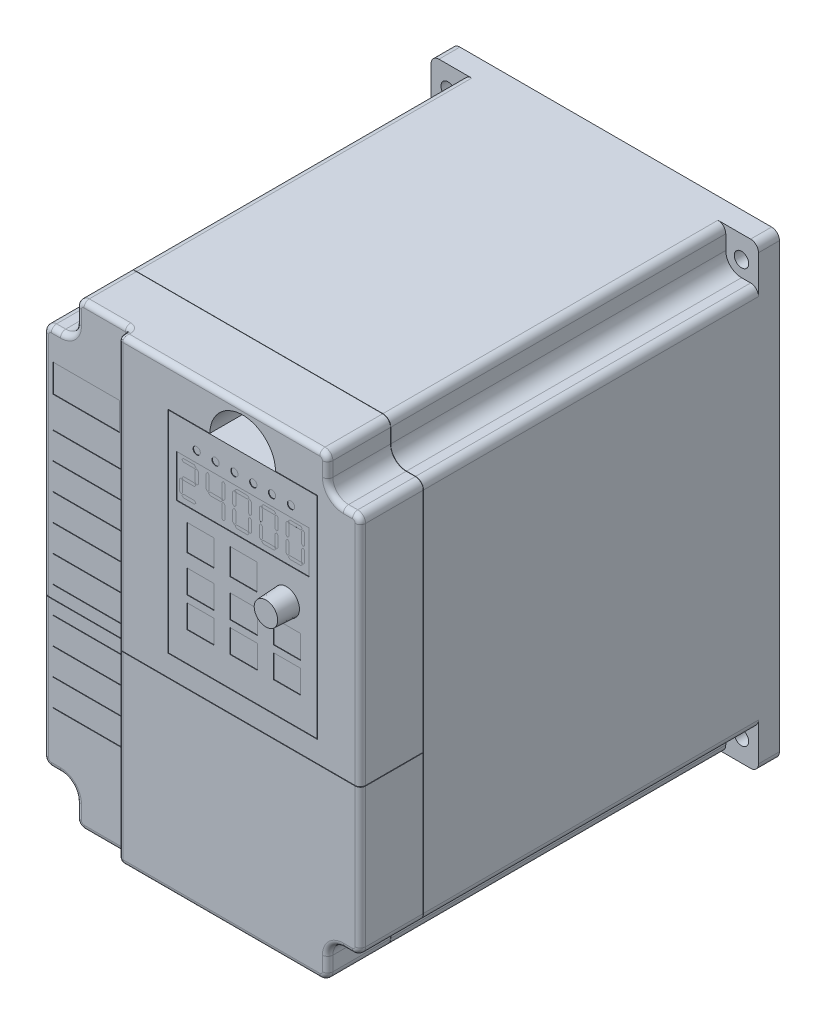
SolidWorks part; units mm, degrees
ref_plane "Front Plane" through (0, 0, 0) normal (0, 0, 1) x (1, 0, 0)
ref_plane "Top Plane" through (0, 0, 0) normal (0, 1, 0) x (1, 0, 0)
ref_plane "Right Plane" through (0, 0, 0) normal (1, 0, 0) x (0, 0, -1)
sketch "Sketch1" plane through (0, 0, 0) normal (0, 0, 1) x (1, 0, 0)
  line L1 (-62.5, -87.5) -> (62.5, -87.5)
  line L2 (-62.5, -87.5) -> (-62.5, 87.5)
  line L3 (-62.5, 87.5) -> (62.5, 87.5)
  line L4 (62.5, -87.5) -> (62.5, 87.5)
  line L5 (0, 87.5) -> (0, -87.5) construction
  line L6 (-62.5, 0) -> (62.5, 0) construction
  point P0 (0, 0)
  dimension "D1" = 125
  dimension "D2" = 175
extrude "Boss-Extrude1" add sketch "Sketch1" along normal blind 160
sketch "Sketch2" plane through (0, 0, 160) normal (0, 0, 1) x (1, 0, 0)
  line L1 (56, -79) -> (-56, -79) construction
  line L2 (56, -79) -> (56, 79) construction
  line L3 (56, 79) -> (-56, 79) construction
  line L4 (-56, -79) -> (-56, 79) construction
  line L5 (0, 79) -> (0, -79) construction
  line L6 (56, 0) -> (-56, 0) construction
  circle A0 centre (-56, 79) radius 2.75
  circle A1 centre (56, 79) radius 2.75
  circle A2 centre (-56, -79) radius 2.75
  circle A3 centre (56, -79) radius 2.75
  point P0 (0, 0)
  dimension "D1" = 5.5
  dimension "D2" = 112
  dimension "D3" = 158
extrude "Cut-Extrude1" cut sketch "Sketch2" against normal through all
sketch "Sketch3" plane through (0, 0, 160) normal (0, 0, 1) x (1, 0, 0)
  line L0 (-50, 79) -> (-50, 87.5)
  line L1 (62.5, 87.5) -> (-62.5, 87.5) construction
  line L2 (-50, 87.5) -> (-62.5, 87.5)
  line L3 (-62.5, 87.5) -> (-62.5, 73)
  line L4 (-62.5, 87.5) -> (-62.5, -87.5) construction
  line L5 (-62.5, 73) -> (-56, 73)
  line L6 (0, 87.5) -> (0, -87.5) construction
  line L7 (-62.5, -87.5) -> (62.5, -87.5) construction
  line L8 (-62.5, 0) -> (62.5, 0) construction
  line L9 (62.5, -87.5) -> (62.5, 87.5) construction
  line L10 (62.5, 73) -> (56, 73)
  line L11 (62.5, 87.5) -> (62.5, 73)
  line L12 (50, 87.5) -> (62.5, 87.5)
  line L13 (50, 79) -> (50, 87.5)
  line L14 (50, -79) -> (50, -87.5)
  line L15 (50, -87.5) -> (62.5, -87.5)
  line L16 (62.5, -87.5) -> (62.5, -73)
  line L17 (62.5, -73) -> (56, -73)
  line L18 (-62.5, -73) -> (-56, -73)
  line L19 (-62.5, -87.5) -> (-62.5, -73)
  line L20 (-50, -87.5) -> (-62.5, -87.5)
  line L21 (-50, -79) -> (-50, -87.5)
  arc A0 (-56, 73) -> (-50, 79) centre (-56, 79) ccw
  arc A1 (56, 73) -> (50, 79) centre (56, 79) cw
  arc A2 (56, -73) -> (50, -79) centre (56, -79) ccw
  arc A3 (-56, -73) -> (-50, -79) centre (-56, -79) cw
  dimension "D1" = 6
extrude "Cut-Extrude2" cut sketch "Sketch3" against normal offset from surface (152 mm away) 8 up to face at (58.75, 79, 0)
sketch "Sketch4" plane through (0, 0, 160) normal (0, 0, 1) x (1, 0, 0)
  line L0 (-21.4754, 179.91) -> (260.5246, 179.91) construction
  line L2 (-29.6938, 97.8376) -> (-77.9459, 97.8376)
  line L3 (-29.6938, 97.8376) -> (-29.6938, -104.6749)
  line L4 (-29.6938, -104.6749) -> (-77.9459, -104.6749)
  line L5 (-77.9459, 97.8376) -> (-77.9459, -104.6749)
  line L6 (-53.8199, -104.6749) -> (-53.8199, 97.8376) construction
  line L7 (-29.6938, -3.4186) -> (-77.9459, -3.4186) construction
  point P206 (-53.8199, -3.4186)
extrude "Cut-Extrude3" cut sketch "Sketch4" against normal blind 4
fillet "Fillet3" radius 1.5 2 edges at (-29.6938, 0, 160) (-29.6938, 0, 156)
fillet "Fillet1" radius 3 12 edges at (-50, 87.5, 82) (-62.5, 73, 82) (-62.5, -73, 82) (-50, -87.5, 82) (50, -87.5, 84) (62.5, -73, 84) (62.5, 73, 84) (50, 87.5, 84) (-62.5, -87.5, 4) (62.5, -87.5, 4) (62.5, 87.5, 4) (-62.5, 87.5, 4)
fillet "Fillet2" radius 2 32 edges at (49.1213, 86.6213, 160) (50, 81.75, 160) (51.7574, 74.7574, 160) (57.75, 73, 160) (61.6213, 72.1213, 160) (62.5, 0, 160) (61.6213, -72.1213, 160) (57.75, -73, 160) (51.7574, -74.7574, 160) (50, -81.75, 160) (49.1213, -86.6213, 160) (9.4031, -87.5, 160) (9.4031, 87.5, 160) (-29.2545, -87.5, 159.5607) (-30.1332, -87.5, 156.4393) (-29.2545, 87.5, 159.5607) (-30.1332, 87.5, 156.4393) (-39.0969, -87.5, 156) (-49.1213, -86.6213, 156) (-50, -81.75, 156) (-51.7574, -74.7574, 156) (-57.75, -73, 156) (-61.6213, -72.1213, 156) (-62.5, 0, 156) (-61.6213, 72.1213, 156) (-57.75, 73, 156) (-51.7574, 74.7574, 156) (-50, 81.75, 156) (-49.1213, 86.6213, 156) (-39.0969, 87.5, 156) (-29.6938, -87.5, 158) (-29.6938, 87.5, 158)
sketch "Sketch5" plane through (0, 0, 160) normal (0, 0, 1) x (1, 0, 0)
  line L0 (78.7819, -16.7409) -> (-90.6907, -16.7409)
  line L1 (12.798, 23.1824) -> (12.798, 14.2684)
  line L2 (-10.721, 71.8528) -> (45.8698, 71.8528)
  line L3 (-10.721, 71.8528) -> (-10.721, -8.4272)
  line L4 (-10.721, -8.4272) -> (45.8698, -8.4272)
  line L5 (45.8698, 71.8528) -> (45.8698, -8.4272)
  line L6 (17.5744, -8.4272) -> (17.5744, 71.8528) construction
  line L7 (-10.721, 31.7128) -> (45.8698, 31.7128) construction
  line L8 (-7.7964, 59.7158) -> (42.9452, 59.7158)
  line L9 (-7.7964, 59.7158) -> (-7.7964, 43.4843)
  line L10 (-7.7964, 43.4843) -> (42.9452, 43.4843)
  line L11 (42.9452, 59.7158) -> (42.9452, 43.4843)
  line L12 (17.5744, 43.4843) -> (17.5744, 59.7158) construction
  line L13 (-7.7964, 51.6) -> (42.9452, 51.6) construction
  line L14 (-3.702, 38.2497) -> (6.6803, 38.2497)
  line L15 (-3.702, 38.2497) -> (-3.702, 28.2467)
  line L16 (-3.702, 28.2467) -> (6.6803, 28.2467)
  line L17 (6.6803, 38.2497) -> (6.6803, 28.2467)
  line L18 (1.4891, 28.2467) -> (1.4891, 38.2497) construction
  line L19 (-3.702, 33.2482) -> (6.6803, 33.2482) construction
  line L20 (12.6404, 38.5061) -> (23.0227, 38.5061)
  line L21 (12.6404, 38.5061) -> (12.6404, 28.5031)
  line L22 (12.6404, 28.5031) -> (23.0227, 28.5031)
  line L23 (23.0227, 38.5061) -> (23.0227, 28.5031)
  line L24 (17.8316, 28.5031) -> (17.8316, 38.5061) construction
  line L25 (12.6404, 33.5046) -> (23.0227, 33.5046) construction
  line L26 (-3.702, 23.1824) -> (6.6803, 23.1824)
  line L27 (-3.702, 23.1824) -> (-3.702, 14.2684)
  line L28 (-3.702, 14.2684) -> (6.6803, 14.2684)
  line L29 (6.6803, 23.1824) -> (6.6803, 14.2684)
  line L30 (1.4891, 14.2684) -> (1.4891, 23.1824) construction
  line L31 (-3.702, 18.7254) -> (6.6803, 18.7254) construction
  line L32 (12.798, 23.1824) -> (23.1803, 23.1824)
  line L33 (23.1803, 23.1824) -> (23.1803, 14.2684)
  line L34 (12.798, 14.2684) -> (23.1803, 14.2684)
  line L35 (29.298, 23.1824) -> (29.298, 14.2684)
  line L36 (29.298, 23.1824) -> (39.6803, 23.1824)
  line L37 (39.6803, 23.1824) -> (39.6803, 14.2684)
  line L38 (29.298, 14.2684) -> (39.6803, 14.2684)
  line L39 (12.798, 11.6824) -> (12.798, 2.7684)
  line L40 (12.798, 11.6824) -> (23.1803, 11.6824)
  line L41 (23.1803, 11.6824) -> (23.1803, 2.7684)
  line L42 (12.798, 2.7684) -> (23.1803, 2.7684)
  line L43 (29.298, 11.6824) -> (29.298, 2.7684)
  line L44 (29.298, 11.6824) -> (39.6803, 11.6824)
  line L45 (39.6803, 11.6824) -> (39.6803, 2.7684)
  line L46 (29.298, 2.7684) -> (39.6803, 2.7684)
  line L47 (-3.702, 11.6824) -> (-3.702, 2.7684)
  line L48 (-3.702, 11.6824) -> (6.6803, 11.6824)
  line L49 (6.6803, 11.6824) -> (6.6803, 2.7684)
  line L50 (-3.702, 2.7684) -> (6.6803, 2.7684)
  line L51 (-58.7795, 39.1914) -> (-31.1938, 39.1914)
  line L52 (-58.7795, 61.6864) -> (-33.3995, 61.6864)
  line L53 (-58.7795, 61.6864) -> (-58.7795, 51.0476)
  line L54 (-58.7795, 51.0476) -> (-33.3995, 51.0476)
  line L55 (-33.3995, 61.6864) -> (-33.3995, 51.0476)
  line L56 (-46.0895, 51.0476) -> (-46.0895, 61.6864) construction
  line L57 (-58.7795, 56.367) -> (-33.3995, 56.367) construction
  line L58 (-31.1938, -85.5) -> (-31.1938, 85.5) construction
  line L59 (-58.7795, 28.9914) -> (-31.1938, 28.9914)
  line L60 (-58.7795, 18.7914) -> (-31.1938, 18.7914)
  line L61 (-58.7795, 8.5914) -> (-31.1938, 8.5914)
  line L62 (-58.7795, -1.6086) -> (-31.1938, -1.6086)
  line L63 (-58.7795, -11.8086) -> (-31.1938, -11.8086)
  line L64 (-58.7795, -22.0086) -> (-31.1938, -22.0086)
  line L65 (-58.7795, -32.2086) -> (-31.1938, -32.2086)
  line L66 (-58.7795, -42.4086) -> (-31.1938, -42.4086)
  line L67 (-58.7795, -52.6086) -> (-31.1938, -52.6086)
  circle A0 centre (34.2415, 30.9924) radius 4.9973
  circle A1 centre (0, 63.7946) radius 1.387
  circle A2 centre (7.2, 63.7946) radius 1.387
  circle A3 centre (14.4, 63.7946) radius 1.387
  circle A4 centre (21.6, 63.7946) radius 1.387
  circle A5 centre (28.8, 63.7946) radius 1.387
  circle A6 centre (36, 63.7946) radius 1.387
  arc A7 (30.1069, 71.8528) -> (5.0418, 71.8528) centre (17.5744, 71.8528) ccw
  point P138 (1.4891, 33.2482)
  point P145 (1.4891, 18.7254)
  point P172 (17.5744, 51.6)
  point P182 (17.8316, 33.5046)
  point P250 (-46.0895, 56.367)
  point P286 (17.5744, 31.7128)
  line M2 (47, 85.5) -> (-28.1938, 85.5)
  dimension "D1" = 3
  dimension "D3" = 6
  dimension "D2" = 2
  dimension "D4" = 10
extrude "Cut-Extrude-Thin1" cut sketch "Sketch5" against normal blind 21.5 thin contours L2 L5 L4 L3 thin type one direction wall 0.2
extrude "Cut-Extrude4" cut sketch "Sketch5<4>" against normal blind 21.5 contours L2 A7 M2 | A7 M2 region at (17.5744, 77.1718, 160)
sketch "Sketch5<4>" plane through (0, 0, 160) normal (0, 0, 1) x (1, 0, 0) same geometry as "Sketch5"
extrude "Cut-Extrude5" cut sketch "Sketch5<5>" against normal blind 0.2 contours L43 L46 L45 L44 | L39 L42 L41 L40 | L47 L50 L49 L48 | L29 L26 L27 L28 | L1 L34 L33 L32 | L35 L38 L37 L36 | A0 | L23 L20 L21 L22 | L17 L14 L15 L16 | L11 L8 L9 L10 | A1 | A2 | A3 | A4 | A5 | A6 region at (17.9891, 18.7254, 160) region at (17.5744, 51.6, 160) region at (1.4891, 33.2482, 160) region at (17.8316, 33.5046, 160) region at (1.4891, 18.7254, 160) region at (34.4891, 18.7254, 160) region at (17.9891, 7.2254, 160) region at (34.4891, 7.2254, 160) region at (1.4891, 7.2254, 160) region at (34.2415, 30.9924, 160) region at (0, 63.7946, 160) region at (7.2, 63.7946, 160) region at (14.4, 63.7946, 160) region at (21.6, 63.7946, 160) region at (28.8, 63.7946, 160) region at (36, 63.7946, 160)
sketch "Sketch5<5>" plane through (0, 0, 160) normal (0, 0, 1) x (1, 0, 0) same geometry as "Sketch5"
extrude "Cut-Extrude-Thin3" cut sketch "Sketch5<6>" against normal offset from surface (4.2 mm away) 0.2 thin contours L51 | L59 | L60 | L61 | L62 | L63 | L64 | L65 | L66 | L67 up to face at (-49.8502, 0, 156) offset beyond the face yes thin type mid plane wall 0.2
sketch "Sketch5<6>" plane through (0, 0, 160) normal (0, 0, 1) x (1, 0, 0) same geometry as "Sketch5"
extrude "Cut-Extrude7" cut sketch "Sketch5<7>" against normal offset from surface (4.2 mm away) 0.2 contours L55 L52 L53 L54 region at (-46.0895, 56.367, 160) up to face at (-46.2476, -4.9693, 156) offset beyond the face yes
sketch "Sketch5<7>" plane through (0, 0, 160) normal (0, 0, 1) x (1, 0, 0) same geometry as "Sketch5"
extrude "Cut-Extrude-Thin4" cut sketch "Sketch5<9>" against normal offset from surface (24 mm away) 20 thin contours L0 up to face at (-46.2476, -4.9693, 156) thin type mid plane wall 0.2
sketch "Sketch5<9>" plane through (0, 0, 160) normal (0, 0, 1) x (1, 0, 0) same geometry as "Sketch5"
sketch "Sketch7" plane through (0, 0, 136) normal (0, 0, 1) x (1, 0, 0)
  line L1 (-69.3976, 94.5086) -> (66.6582, 94.5086)
  line L2 (-69.3976, 94.5086) -> (-69.3976, -92.2258)
  line L3 (-69.3976, -92.2258) -> (66.6582, -92.2258)
  line L4 (66.6582, 94.5086) -> (66.6582, -92.2258)
  line L5 (-1.3697, -92.2258) -> (-1.3697, 94.5086) construction
  line L6 (-69.3976, 1.1414) -> (66.6582, 1.1414) construction
  point P192 (-1.3697, 1.1414)
extrude "Cut-Extrude8" cut sketch "Sketch7" against normal blind 0.1
sketch "Sketch8" plane through (0, 0, 159.8) normal (0, 0, 1) x (1, 0, 0)
  line L2 (-7.7964, 45.4843) -> (42.9452, 45.4843)
  line L3 (-7.7964, 45.4843) -> (42.9452, 45.4843) construction
  text T0 "24000" font "Seven Segment" height 13
  dimension "D1" = 2
extrude "Cut-Extrude9" cut sketch "Sketch8" against normal blind 0.001
sketch "Sketch9" plane through (0, 0, 159.8) normal (0, 0, 1) x (1, 0, 0)
  circle A2 centre (34.2415, 30.9924) radius 4.8973
  circle A3 centre (34.2415, 30.9924) radius 4.8973
  dimension "D1" = 0.1
extrude "Boss-Extrude2" add sketch "Sketch9" along normal blind 8 draft 3
